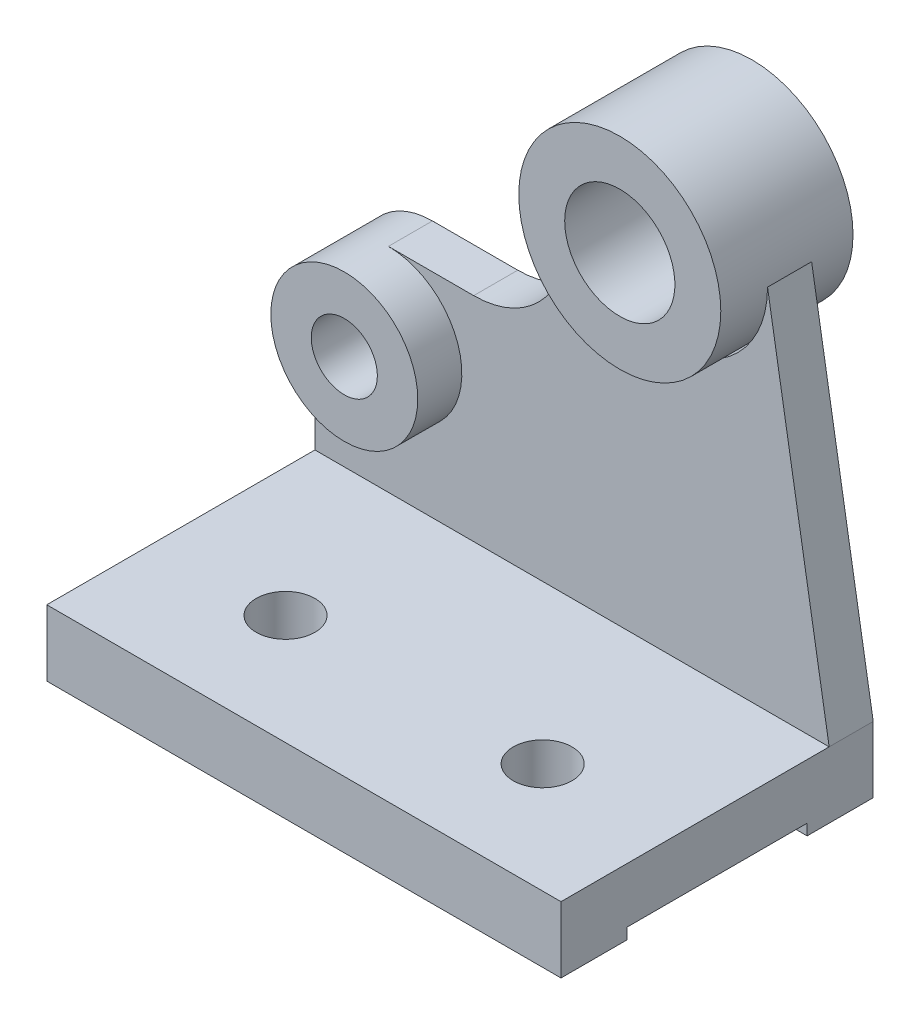
SolidWorks part; units mm, degrees
ref_plane "Front Plane" through (0, 0, 0) normal (0, 0, 1) x (1, 0, 0)
ref_plane "Top Plane" through (0, 0, 0) normal (0, 1, 0) x (1, 0, 0)
ref_plane "Right Plane" through (0, 0, 0) normal (1, 0, 0) x (0, 0, -1)
sketch "Sketch1" plane through (0, 0, 0) normal (0, 0, 1) x (1, 0, 0)
  line L0 (123.228, 118) -> (140, 18)
  line L1 (0, 18) -> (140, 18)
  line L2 (0, 18) -> (0, 56)
  line L3 (20, 76) -> (43.228, 76)
  line L4 (68.228, 118) -> (68.228, 101)
  line L5 (0, 18) -> (0, 0)
  line L6 (0, 0) -> (140, 0)
  line L7 (140, 0) -> (140, 18)
  circle A0 centre (20, 56) radius 20
  circle A1 centre (20, 56) radius 9
  circle A2 centre (95.728, 118) radius 27.5
  circle A3 centre (95.728, 118) radius 15
  arc A4 (43.228, 76) -> (68.228, 101) centre (43.228, 101) ccw
  point P18 (0, 0)
  point P19 (0, 0)
  point P20 (0, 0)
  point P22 (11.4479, 56)
  point P23 (64.5779, 58.2897)
  point P24 (0, 36.5596)
  point P25 (0, 56)
  point P26 (95.728, 118)
  point P27 (0, 0)
  dimension "D1" = 140
  dimension "D6" = 18
  dimension "D7" = 25
  dimension "D8" = 55
  dimension "D9" = 30
  dimension "D2" = 18
  dimension "D3" = 38
  dimension "D4" = 20
  dimension "D5" = 100
extrude "Boss-Extrude1" add sketch "Sketch1" along normal blind 12 contours A4 L3 A0 L2 L1 L0 A2 L4 region at (80.8523, 52.0483, 0)
extrude "Boss-Extrude2" add sketch "Sketch1<3>" along normal blind 24 contours A0 A1 region at (6.2579, 69.7421, 0)
sketch "Sketch1<3>" plane through (0, 0, 0) normal (0, 0, 1) x (1, 0, 0) same geometry as "Sketch1"
extrude "Boss-Extrude3" add sketch "Sketch1<4>" along normal blind 85 contours L6 L7 L1 L5 region at (70, 9, 0)
sketch "Sketch1<4>" plane through (0, 0, 0) normal (0, 0, 1) x (1, 0, 0) same geometry as "Sketch1"
ref_plane "Plane1" through (0, 0, 6) normal (0, 0, -1) x (-1, 0, 0)
sketch "Sketch2" plane through (0, 0, 6) normal (0, 0, -1) x (-1, 0, 0)
  line L0 (0, 0) -> (-140, 0) construction
  line L1 (-140, 0) -> (-140, 18) construction
  circle A0 centre (-95, 118) radius 27.5
  circle A1 centre (-95, 118) radius 15
  dimension "D3" = 55
  dimension "D4" = 30
  dimension "D1" = 118
  dimension "D2" = 45
extrude "Boss-Extrude4" add sketch "Sketch2" along normal mid plane 36
sketch "Sketch3" plane through (0, 18, 0) normal (0, 1, 0) x (1, 0, 0)
  line L0 (0, -85) -> (0, -12) construction
  line L1 (0, -85) -> (140, -85) construction
  circle A0 centre (105, -55) radius 8
  circle A1 centre (35, -55) radius 8
  dimension "D1" = 16
  dimension "D2" = 35
  dimension "D3" = 70
  dimension "D4" = 30
extrude "Cut-Extrude1" cut sketch "Sketch3" against normal through all
sketch "Sketch5" plane through (0, 0, 0) normal (-1, 0, 0) x (0, 0, 1)
  line L0 (18, 0) -> (18, 3)
  line L1 (85, 0) -> (0, 0) construction
  line L2 (18, 3) -> (67, 3)
  line L3 (67, 3) -> (67, 0)
  line L4 (67, 0) -> (18, 0)
  point P4 (0, 0)
  dimension "D1" = 18
  dimension "D2" = 18
  dimension "D3" = 3
extrude "Cut-Extrude2" cut sketch "Sketch5" against normal through all
